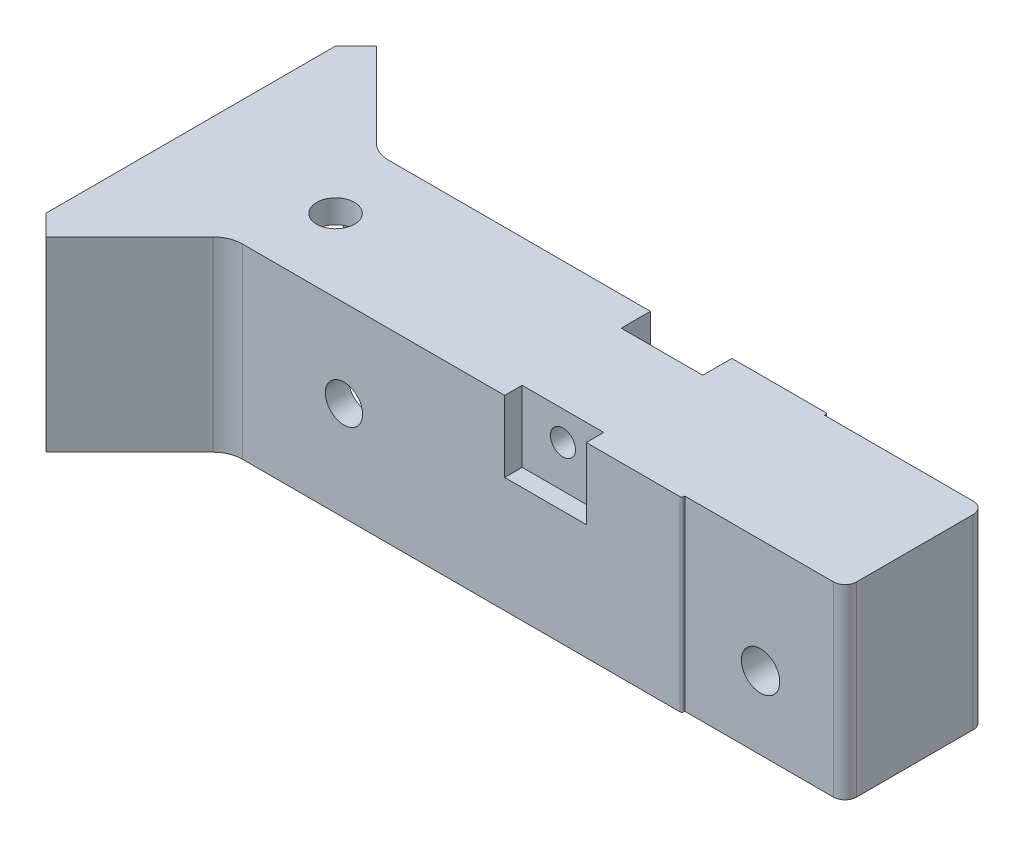
SolidWorks part; units mm, degrees
ref_plane "Front Plane" through (0, 0, 0) normal (0, 0, 1) x (1, 0, 0)
ref_plane "Top Plane" through (0, 0, 0) normal (0, 1, 0) x (1, 0, 0)
ref_plane "Right Plane" through (0, 0, 0) normal (1, 0, 0) x (0, 0, -1)
sketch "Sketch1" plane through (0, 0, 0) normal (0, 1, 0) x (1, 0, 0)
  line L0 (0, 7.55) -> (-32.6, 7.55)
  line L2 (0, 7.55) -> (0, -7.55)
  line L5 (-49.8744, -24.8244) -> (-46.3388, -28.3599)
  line L6 (-32.6, -7.55) -> (-49.8744, -24.8244)
  line L7 (-32.6, 7.55) -> (-49.8744, 24.8244)
  line L8 (-49.8744, 24.8244) -> (-46.3388, 28.3599)
  line L9 (-1000, 0) -> (49000, 0) construction
  line L10 (0, -7.55) -> (-32.6, -7.55)
  line L11 (75, -12.55) -> (75, 12.45)
  line L12 (-46.3388, 28.3599) -> (-30.4289, 12.45)
  line L13 (-30.4289, 12.45) -> (75, 12.45)
  line L14 (-46.3388, -28.3599) -> (-30.5289, -12.55)
  line L15 (-30.5289, -12.55) -> (75, -12.55)
  point P0 (0, 0)
  point P13 (0, 0)
  dimension "D1" = 7.55
  dimension "D2" = 135
  dimension "D3" = 45
  dimension "D4" = 22.5
  dimension "D5" = 32.6
  dimension "D6" = 45
  dimension "D7" = 5
  dimension "D8" = 5
  dimension "D9" = 5
  dimension "D10" = 4.9
  dimension "D11" = 90
  dimension "D12" = 90
  dimension "D13" = 75
extrude "Boss-Extrude1" add sketch "Sketch1" along normal blind 27
sketch "Sketch2" plane through (0, 27, 0) normal (0, 1, 0) x (1, 0, 0)
  line L0 (-49.8744, 24.8244) -> (-49.8744, -24.8244)
  line L1 (0, 7.55) -> (0, -7.55) construction
  line L12 (-30.4289, 12.45) -> (-46.3388, 28.3599)
  line L13 (-46.3388, 28.3599) -> (-49.8744, 24.8244)
  line L14 (-49.8744, 24.8244) -> (-32.6, 7.55)
  line L15 (-32.6, 7.55) -> (0, 7.55)
  line L16 (0, 7.55) -> (0, -7.55)
  line L17 (0, -7.55) -> (-32.6, -7.55)
  line L18 (-32.6, -7.55) -> (-49.8744, -24.8244)
  line L19 (-49.8744, -24.8244) -> (-46.3388, -28.3599)
  line L20 (-46.3388, -28.3599) -> (-30.5289, -12.55)
  line L21 (-30.5289, -12.55) -> (75, -12.55)
  line L22 (75, -12.55) -> (75, 12.45)
  line L23 (75, 12.45) -> (-30.4289, 12.45)
  line L24 (-30.4289, 12.45) -> (-46.3388, 28.3599)
  line L25 (-46.3388, 28.3599) -> (-49.8744, 24.8244)
  line L31 (-49.8744, -24.8244) -> (-46.3388, -28.3599)
  line L32 (-46.3388, -28.3599) -> (-30.5289, -12.55)
  line L33 (-30.5289, -12.55) -> (75, -12.55)
  line L34 (75, -12.55) -> (75, 12.45)
  line L35 (75, 12.45) -> (-30.4289, 12.45)
  circle A0 centre (-25, 0) radius 3.25
  dimension "D3" = 6.5
  dimension "D2" = 25
  dimension "D1" = 0
extrude "Boss-Extrude2" add sketch "Sketch2" along normal blind 5
sketch "Sketch3" plane through (0, 0, 12.55) normal (0, 0, 1) x (1, 0, 0)
  line L0 (0, 27) -> (0, 0) construction
  line L3 (0, 27) -> (-32.6, 27) construction
  circle A0 centre (-11, 17) radius 3.2
  dimension "D1" = 6.4
  dimension "D2" = 11
  dimension "D3" = 10
extrude "Cut-Extrude1" cut sketch "Sketch3" against normal through all both and the other way through all
sketch "Sketch4" plane through (0, 32, 0) normal (0, 1, 0) x (1, 0, 0)
  line L0 (75, 12.45) -> (-30.4289, 12.45) construction
  line L1 (18.5857, 12.45) -> (28.5857, 12.45)
  line L2 (18.5857, 12.45) -> (18.5857, 7.45)
  line L3 (18.5857, 7.45) -> (28.5857, 7.45)
  line L4 (28.5857, 12.45) -> (28.5857, 7.45)
  line L5 (18.5857, 12.45) -> (28.5857, 7.45) construction
  line L6 (18.5857, 7.45) -> (28.5857, 12.45) construction
  line L7 (-30.5289, -12.55) -> (75, -12.55) construction
  line L8 (18.5857, -12.55) -> (28.5857, -12.55)
  line L9 (18.5857, -12.55) -> (18.5857, -9.55)
  line L10 (18.5857, -9.55) -> (28.5857, -9.55)
  line L11 (28.5857, -12.55) -> (28.5857, -9.55)
  line L12 (18.5857, -12.55) -> (28.5857, -9.55) construction
  line L13 (18.5857, -9.55) -> (28.5857, -12.55) construction
  line L14 (75, -12.55) -> (75, 12.45) construction
  point P4 (23.5857, 9.95)
  point P11 (23.5857, -11.05)
  dimension "D1" = 5
  dimension "D2" = 3
  dimension "D3" = 10
  dimension "D4" = 46.4143
extrude "Cut-Extrude2" cut sketch "Sketch4" against normal blind 10.2
sketch "Sketch5" plane through (0, 0, -7.45) normal (0, 0, -1) x (-1, 0, 0)
  line L0 (-18.5857, 21.8) -> (-18.5857, 32) construction
  line L1 (-28.5857, 32) -> (-18.5857, 32) construction
  line L2 (-28.5857, 32) -> (-28.5857, 22) construction
  line L3 (-28.5857, 22) -> (-18.5857, 22) construction
  line L4 (-18.5857, 32) -> (-18.5857, 22) construction
  line L5 (-28.5857, 32) -> (-18.5857, 22) construction
  line L6 (-28.5857, 22) -> (-18.5857, 32) construction
  circle A0 centre (-23.5857, 27) radius 2.15
  point P4 (-23.5857, 27)
  dimension "D2" = 4.3
  dimension "D1" = 10
extrude "Cut-Extrude3" cut sketch "Sketch5" against normal through all both and the other way through all
sketch "Sketch6" plane through (0, 0, -12.45) normal (0, 0, -1) x (-1, 0, 0)
  line L1 (-75, 32) -> (-28.5857, 32) construction
  line L3 (-75, 32) -> (-75, 0) construction
  circle A0 centre (-60, 12.5) radius 3.3
  dimension "D1" = 6.6
  dimension "D2" = 19.5
  dimension "D3" = 15
extrude "Cut-Extrude4" cut sketch "Sketch6" against normal through all both and the other way through all
sketch "Sketch8" plane through (0, 0, 0) normal (0, 0, 1) x (1, 0, 0)
  line L0 (18.5857, 21.8) -> (28.5857, 21.8) construction
  line L1 (16.5857, 34.2) -> (30.5857, 34.2)
  line L2 (16.5857, 34.2) -> (16.5857, 19.8)
  line L3 (16.5857, 19.8) -> (30.5857, 19.8)
  line L4 (30.5857, 34.2) -> (30.5857, 19.8)
  line L5 (16.5857, 34.2) -> (30.5857, 19.8) construction
  line L6 (16.5857, 19.8) -> (30.5857, 34.2) construction
  line L7 (28.5857, 21.8) -> (28.5857, 32) construction
  point P0 (23.5857, 27)
  dimension "D1" = 2
  dimension "D2" = 2
extrude "Cut-Extrude5" cut sketch "Sketch8" along normal blind 10 from surface starting at face at (21.4357, 27, 9.55)
extrude "Cut-Extrude6" cut sketch "Sketch8<2>" against normal blind 10 from surface starting at face at (25.7357, 27, -7.45)
sketch "Sketch8<2>" plane through (0, 0, 0) normal (0, 0, 1) x (1, 0, 0) same geometry as "Sketch8"
sketch "Sketch9" plane through (0, 0, 0) normal (0, -1, 0) x (1, 0, 0)
  line L1 (75, 12.55) -> (47, 12.55)
  line L2 (75, 12.55) -> (75, 12.05)
  line L3 (74.5, 12.05) -> (47, 12.05)
  line L4 (47, 12.55) -> (47, 12.05)
  line L5 (75, 12.55) -> (47, 12.05) construction
  line L6 (61, 12.3) -> (47, 12.55) construction
  line L7 (75, -12.45) -> (47, -12.45)
  line L8 (75, -12.45) -> (75, -11.95)
  line L9 (74.5, -11.95) -> (47, -11.95)
  line L10 (47, -12.45) -> (47, -11.95)
  line L11 (75, -12.45) -> (47, -11.95) construction
  line L12 (61, -12.2) -> (47, -12.45) construction
  line L14 (75, -11.95) -> (75, 12.05)
  line L16 (74.5, -11.95) -> (74.5, 12.05)
  line L17 (75, -11.95) -> (74.5, 12.05) construction
  line L18 (75, 12.05) -> (74.5, -11.95) construction
  point P4 (61, 12.3)
  point P10 (61, -12.2)
  point P14 (74.75, 0.05)
  dimension "D1" = 0.5
  dimension "D2" = 28
  dimension "D3" = 0.5
extrude "Cut-Extrude7" cut sketch "Sketch9" against normal through all
sketch "Sketch10" plane through (0, 27, 0) normal (0, -1, 0) x (1, 0, 0)
  line L33 (-50.8744, 27.2386) -> (-50.8744, -27.2386)
  line L34 (-50.8744, -27.2386) -> (-32.1858, -8.55)
  line L35 (-32.1858, -8.55) -> (1, -8.55)
  line L36 (1, -8.55) -> (1, 8.55)
  line L37 (1, 8.55) -> (-32.1858, 8.55)
  line L38 (-32.1858, 8.55) -> (-50.8744, 27.2386)
  line L39 (-50.8744, 27.2386) -> (-50.8744, -27.2386)
  line L40 (-50.8744, -27.2386) -> (-32.1858, -8.55)
  line L41 (-32.1858, -8.55) -> (1, -8.55)
  line L42 (1, -8.55) -> (1, 8.55)
  line L43 (1, 8.55) -> (-32.1858, 8.55)
  line L44 (-32.1858, 8.55) -> (-50.8744, 27.2386)
  dimension "D1" = 1
extrude "Cut-Extrude8" cut sketch "Sketch10" along normal through all from offset 1 offset against normal yes
fillet "Fillet3" radius 5 2 edges at (-30.4289, 16, -12.45) (-30.5289, 16, 12.55)
fillet "Fillet4" radius 2 2 edges at (74.5, 16, -11.95) (74.5, 16, 12.05)
fillet "Fillet5" radius 0.3 2 edges at (47, 16, -12.45) (47, 16, 12.55)
